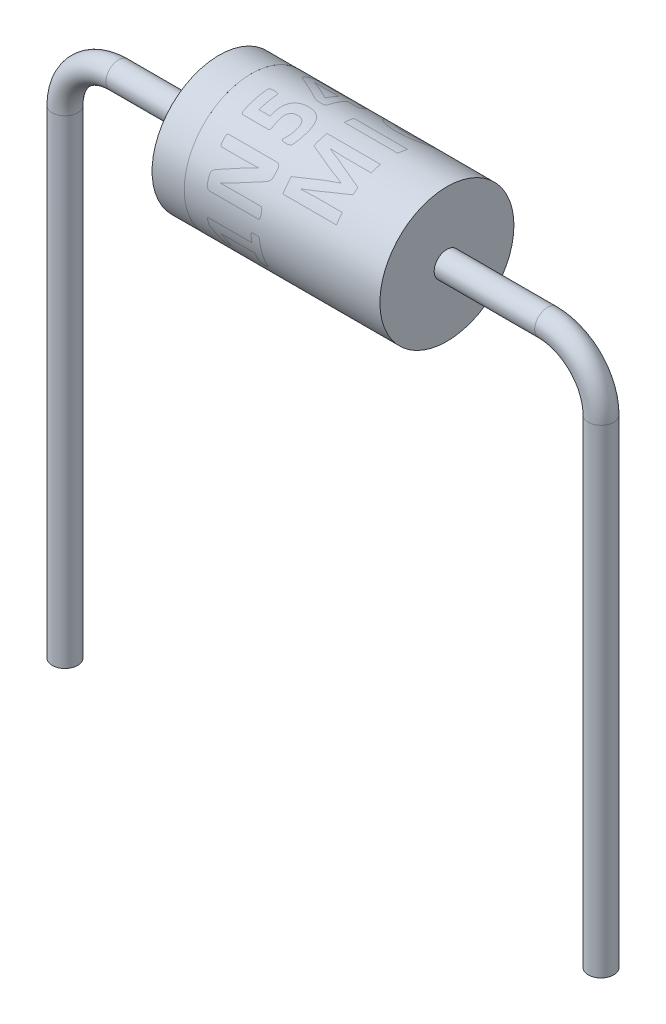
SolidWorks part; units mm, degrees
other "Diode"
other "Cathode Silver Band"
other "Wire"
ref_plane "Front Plane" through (0, 0, 0) normal (0, 0, 1) x (1, 0, 0)
ref_plane "Top Plane" through (0, 0, 0) normal (0, 1, 0) x (1, 0, 0)
ref_plane "Right Plane" through (0, 0, 0) normal (1, 0, 0) x (0, 0, -1)
sketch "Sketch1" plane through (0, 0, 0) normal (1, 0, 0) x (0, 0, -1)
  circle A0 centre (0, 0) radius 2.5
  circle A1 centre (0, 0) radius 0.475
  dimension "D1" = 5
  dimension "D2" = 0.95
extrude "Boss-Extrude1" add sketch "Sketch1" along normal mid plane 8.5
sketch "Sketch2" plane through (-4.25, 0, 0) normal (-1, 0, 0) x (0, 0, 1)
  circle A1 centre (0, 0) radius 2.5 construction
  circle A2 centre (0, 0) radius 2.49
  circle A3 centre (0, 0) radius 2.49
  circle A4 centre (0, 0) radius 2.5
  dimension "D1" = 0.01
extrude "Cut-Extrude1" cut sketch "Sketch2" against normal blind 1.2
sketch "Sketch3" plane through (-3.05, 0, 0) normal (-1, 0, 0) x (0, 0, 1)
  circle A0 centre (0, 0) radius 2.49 construction
  circle A1 centre (0, 0) radius 2.49
  circle A2 centre (0, 0) radius 2.5 construction
  circle A3 centre (0, 0) radius 2.5
extrude "Boss-Extrude2" add sketch "Sketch3" along normal up to surface (1.2 mm away) separate body up to face at (-4.25, 0, -0.475)
ref_plane "Plane1" through (0, 5, 0) normal (0, 1, 0) x (1, 0, 0)
sketch "Sketch4" plane through (0, 5, 0) normal (0, 1, 0) x (1, 0, 0)
  line L0 (-0.25, 7.5) -> (-0.25, -7.5) construction
  line L1 (-0.25, 0) -> (-4.25, 0) construction
  line L2 (-4.25, 2.5) -> (-4.25, -2.5) construction
  line L4 (-0.25, 0) -> (2.25, 0) construction
  line L5 (2.25, 7.5) -> (2.25, -7.5) construction
  text T0 "1N5408" font "Calibri" height 2
  text T1 "MIC" font "Corbel" height 2
  dimension "D1" = 4
  dimension "D2" = 15
  dimension "D3" = 2.5
wrap "Wrap1" sketch "Sketch4" wrap type scribe source sketch "Sketch4" face at (4.25, 0, -2.5)
sketch "Sketch5" plane through (0, 0, 0) normal (0, 0, 1) x (1, 0, 0)
  line L0 (0, 0) -> (-8, 0)
  line L1 (-10, -2) -> (-10, -19.8584)
  line L2 (0, 0) -> (8, 0)
  line L3 (10, -2) -> (10, -19.8584)
  arc A0 (-8, 0) -> (-10, -2) centre (-8, -2) ccw
  arc A1 (8, 0) -> (10, -2) centre (8, -2) cw
  dimension "D2" = 2
  dimension "D3" = 58
  dimension "D1" = 20
sketch "Sketch6" plane through (0, 0, 0) normal (1, 0, 0) x (0, 0, -1)
  circle A0 centre (0, 0) radius 0.475
  dimension "D1" = 0.95
sweep "Sweep1" add profiles "Sketch6" path "Sketch5"
